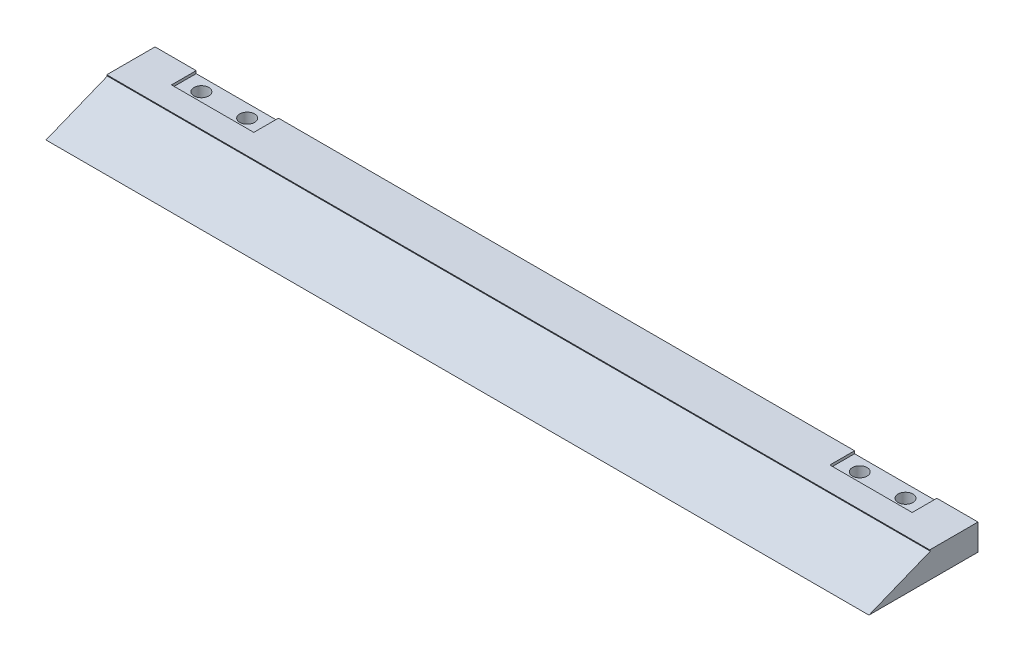
SolidWorks part; units mm, degrees
ref_plane "Front Plane" through (0, 0, 0) normal (0, 0, 1) x (1, 0, 0)
ref_plane "Top Plane" through (0, 0, 0) normal (0, 1, 0) x (1, 0, 0)
ref_plane "Right Plane" through (0, 0, 0) normal (1, 0, 0) x (0, 0, -1)
sketch "Sketch1" plane through (0, 0, 0) normal (0, 1, 0) x (1, 0, 0)
  line L1 (-100, -15) -> (100, -15)
  line L2 (-100, -15) -> (-100, 15)
  line L3 (-100, 15) -> (100, 15)
  line L4 (100, -15) -> (100, 15)
  line L5 (-100, -15) -> (100, 15) construction
  line L6 (-100, 15) -> (100, -15) construction
  point P0 (0, 0)
  dimension "D1" = 200
  dimension "D2" = 30
extrude "Base" add sketch "Sketch1" along normal blind 6.35
ref_plane "Midplane" through (0, 0, 0) normal (1, 0, 0) x (0, 0, -1)
sketch "Sketch2" plane through (100, 0, 0) normal (1, 0, 0) x (0, 0, -1)
  line L0 (-11.5, 0) -> (4.2695, 6.35)
  line L1 (-15, 0) -> (15, 0) construction
  line L2 (-15, 6.35) -> (15, 6.35) construction
  line L3 (4.2695, 6.35) -> (4.2695, 0)
  line L4 (4.2695, 0) -> (-11.5, 0)
  line L5 (-15, 6.35) -> (-15, 0) construction
  line L7 (4.2695, 6.35) -> (-15, 6.35)
  line L8 (-15, 6.35) -> (-15, 0)
  line L9 (-15, 0) -> (-11.5, 0)
  line L10 (3.409, 6.0035) -> (3.2695, 6.35)
  line M3 (-15, 0) -> (15, 0)
  line M5 (15, 6.35) -> (-15, 6.35)
  line M6 (-15, 6.35) -> (-15, 0)
  dimension "D1" = 17
  dimension "D2" = 3.5
  dimension "D3" = 1
extrude "WedgeCut" cut sketch "Sketch2" against normal up to next contours L0 M3 M5 M6 region at (100, 3.9024, 8.4264)
sketch "Sketch3" plane through (0, 6.35, 0) normal (0, 1, 0) x (1, 0, 0)
  line L0 (-100, 15) -> (-100, 3.2695) construction
  line L1 (-90, 9) -> (-70, 9)
  line L2 (-90, 9) -> (-90, 15)
  line L3 (-90, 15) -> (-70, 15)
  line L4 (-70, 9) -> (-70, 15)
  line L5 (-90, 9) -> (-70, 15) construction
  line L6 (-90, 15) -> (-70, 9) construction
  line L7 (70, 15) -> (90, 15)
  line L8 (70, 15) -> (70, 9)
  line L9 (70, 9) -> (90, 9)
  line L10 (90, 15) -> (90, 9)
  line L11 (70, 15) -> (90, 9) construction
  line L12 (70, 9) -> (90, 15) construction
  line L13 (100, 15) -> (-100, 15) construction
  line L14 (100, 3.2695) -> (100, 15) construction
  point P0 (-80, 12)
  point P5 (80, 12)
  dimension "D1" = 6
  dimension "D2" = 20
  dimension "D3" = 10
  dimension "D4" = 20
  dimension "D5" = 10
  dimension "D6" = 6
extrude "Hinge Cutout" cut sketch "Sketch3" against normal blind 0.635
sketch "Sketch4" plane through (0, 5.715, 0) normal (0, 1, 0) x (1, 0, 0)
  line L0 (90, 15) -> (70, 15) construction
  circle A0 centre (74.4374, 11.825) radius 1.8034
  circle A1 centre (85.5626, 11.825) radius 1.8034
  point P6 (80, 15)
  point P7 (0, 0)
  dimension "D5" = 3.6068
  dimension "D6" = 3.6068
  dimension "D1" = 5.5626
  dimension "D2" = 5.5626
  dimension "D3" = 3.175
  dimension "D4" = 3.175
extrude "Hinge Hole Cut" cut sketch "Sketch4" against normal up to next
sketch "Sketch5" plane through (0, 0, 0) normal (0, -1, 0) x (1, 0, 0)
  line L1 (71.9124, -14.35) -> (76.9624, -14.35)
  line L2 (71.9124, -14.35) -> (71.9124, -9.3)
  line L3 (71.9124, -9.3) -> (76.9624, -9.3)
  line L4 (76.9624, -14.35) -> (76.9624, -9.3)
  line L5 (71.9124, -14.35) -> (76.9624, -9.3) construction
  line L6 (71.9124, -9.3) -> (76.9624, -14.35) construction
  line L7 (83.0376, -14.35) -> (88.0876, -14.35)
  line L8 (83.0376, -14.35) -> (83.0376, -9.3)
  line L9 (83.0376, -9.3) -> (88.0876, -9.3)
  line L10 (88.0876, -14.35) -> (88.0876, -9.3)
  line L11 (83.0376, -14.35) -> (88.0876, -9.3) construction
  line L12 (83.0376, -9.3) -> (88.0876, -14.35) construction
  point P0 (74.4374, -11.825)
  point P6 (85.5626, -11.825)
  dimension "D1" = 5.05
  dimension "D2" = 5.05
  dimension "D3" = 5.05
  dimension "D4" = 5.05
extrude "Hinge Nut Cut" cut sketch "Sketch5" against normal blind 2
mirror "Hinge Hole Mirror" about plane through (0, 0, 0) normal (1, 0, 0) of "Hinge Nut Cut", "Hinge Hole Cut"
